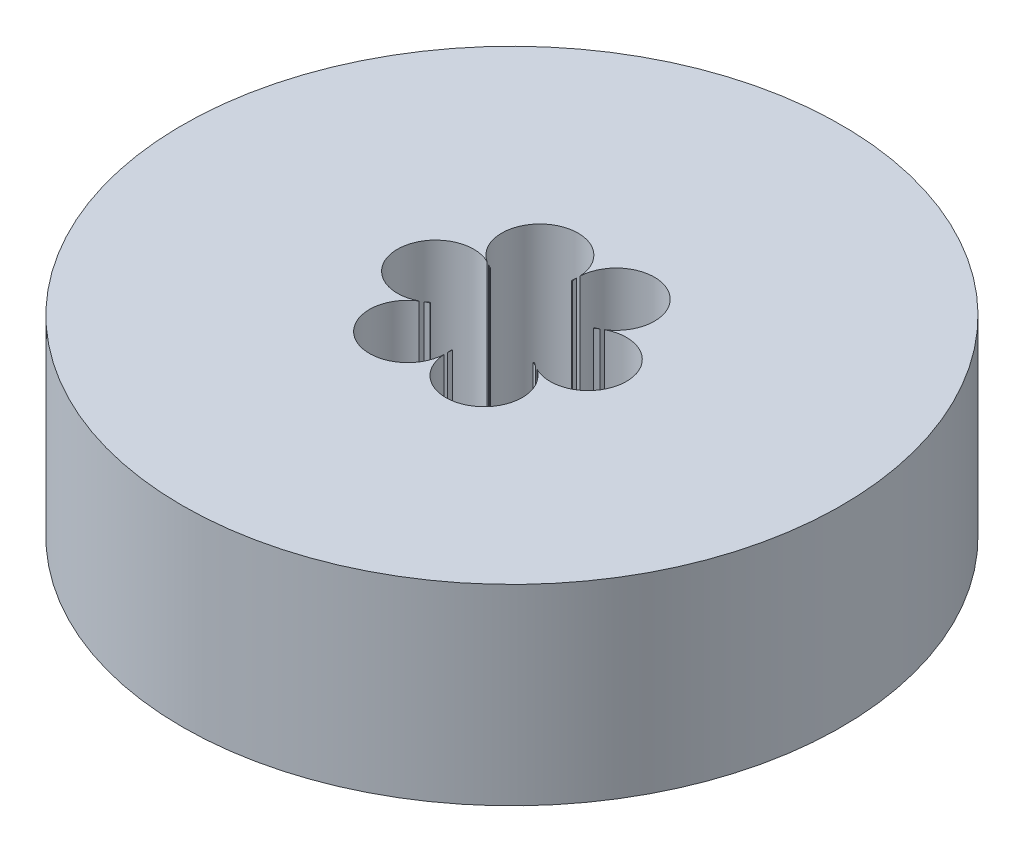
SolidWorks part; units mm, degrees
ref_plane "Front Plane" through (0, 0, 0) normal (0, 0, 1) x (1, 0, 0)
ref_plane "Top Plane" through (0, 0, 0) normal (0, 1, 0) x (1, 0, 0)
ref_plane "Right Plane" through (0, 0, 0) normal (1, 0, 0) x (0, 0, -1)
sketch "Sketch1" plane through (0, 0, 0) normal (0, 1, 0) x (1, 0, 0)
  circle A0 centre (0, 0) radius 27.5
  dimension "FLANGE_OD" = 55
extrude "Boss-Extrude1" add sketch "Sketch1" along normal blind 16
sketch "Sketch2" plane through (0, 0, 0) normal (0, 1, 0) x (1, 0, 0)
  circle A0 centre (0, 0) radius 5
  dimension "BORE_D" = 10
extrude "Cut-Extrude1" cut sketch "Sketch2" along normal through all
sketch "Sketch3" plane through (0, 16, 0) normal (0, 1, 0) x (1, 0, 0)
  circle A0 centre (0, 0) radius 6.3704 construction
  circle A1 centre (-6.3704, 0) radius 3.1886
  dimension "BOLT_D" = 6.3772
  dimension "BOLT_PCD" = 12.7409
extrude "Cut-Extrude2" cut sketch "Sketch3" against normal blind 15.2756
pattern_circular "CirPattern1" count 6 over 360 about axis through (0, 0, 0) along (0, 1, 0) of "Cut-Extrude2"
